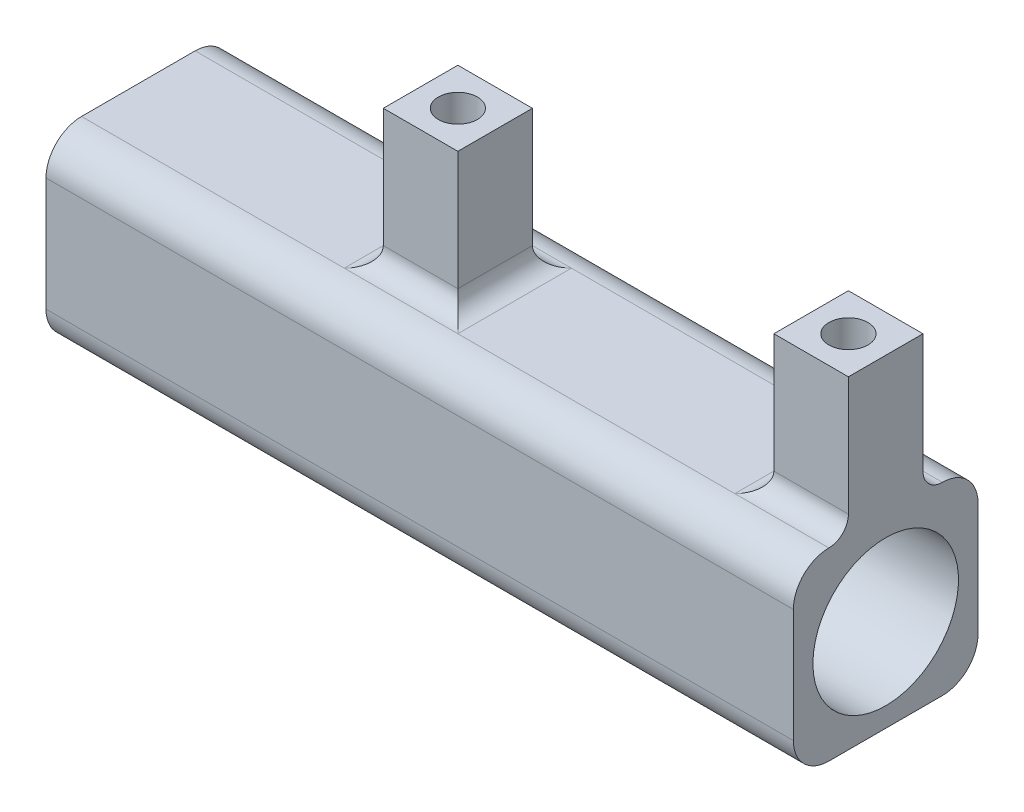
SolidWorks part; units mm, degrees
ref_plane "Front Plane" through (0, 0, 0) normal (0, 0, 1) x (1, 0, 0)
ref_plane "Top Plane" through (0, 0, 0) normal (0, 1, 0) x (1, 0, 0)
ref_plane "Right Plane" through (0, 0, 0) normal (1, 0, 0) x (0, 0, -1)
sketch "Sketch1" plane through (0, 0, 0) normal (0, 0, 1) x (1, 0, 0)
  line L1 (-52.625, 13) -> (52.625, 13)
  line L2 (-52.625, 13) -> (-52.625, -13)
  line L3 (-52.625, -13) -> (52.625, -13)
  line L4 (52.625, 13) -> (52.625, -13)
  line L7 (-12.875, 13) -> (-2.375, 13)
  line L8 (-12.875, 13) -> (-12.875, 32.5)
  line L9 (-12.875, 32.5) -> (-2.375, 32.5)
  line L10 (-2.375, 13) -> (-2.375, 32.5)
  line L11 (42.125, 13) -> (52.625, 13)
  line L12 (42.125, 13) -> (42.125, 32.5)
  line L13 (42.125, 32.5) -> (52.625, 32.5)
  line L14 (52.625, 13) -> (52.625, 32.5)
  point P0 (0, 0)
  point P15 (-52.625, 0)
  point P16 (47.375, 32.5)
  point P18 (-7.625, 32.5)
  point P24 (0, 13)
  dimension "D1" = 26
  dimension "D2" = 45
  dimension "D3" = 10.5
  dimension "D4" = 55
  dimension "D5" = 0
  dimension "D6" = 19.5
extrude "Boss-Extrude1" add sketch "Sketch1" along normal mid plane 26 contours L4 L1 L2 L3 region at (0, 0, 0)
extrude "Boss-Extrude2" add sketch "Sketch1<3>" along normal mid plane 10.5 contours L1 L10 L9 L8 | L1 L14 L13 L12 region at (-7.625, 22.75, 0) region at (47.375, 22.75, 0)
sketch "Sketch1<3>" plane through (0, 0, 0) normal (0, 0, 1) x (1, 0, 0) same geometry as "Sketch1"
sketch "Sketch2" plane through (-52.625, 0, 0) normal (-1, 0, 0) x (0, 0, 1)
  circle A0 centre (0, 0) radius 10.25
  dimension "D1" = 20.5
extrude "Cut-Extrude1" cut sketch "Sketch2" against normal through all
sketch "Sketch3" plane through (0, 32.5, 0) normal (0, 1, 0) x (1, 0, 0)
  line L0 (-12.875, 5.25) -> (-2.375, 5.25) construction
  line L1 (-2.375, -5.25) -> (-2.375, 5.25) construction
  line L2 (42.125, 5.25) -> (52.625, 5.25) construction
  circle A0 centre (-7.625, 0) radius 2.75
  circle A1 centre (47.375, 0) radius 2.75
  point P4 (-2.375, 0)
  point P5 (-7.625, 5.25)
  point P6 (0, 0)
  point P11 (0, 0)
  point P12 (47.375, 5.25)
  dimension "D1" = 5.5
extrude "Cut-Extrude2" cut sketch "Sketch3" against normal up to next
fillet "Fillet1" radius 5 4 edges at (0, -13, -13) (0, 13, -13) (0, -13, 13) (0, 13, 13)
fillet "Fillet4" radius 2.75 7 edges at (-12.875, 13, 0) (42.125, 13, 0) (-2.375, 13, 0) (47.375, 13, -5.25) (47.375, 13, 5.25) (-7.625, 13, 5.25) (-7.625, 13, -5.25)
